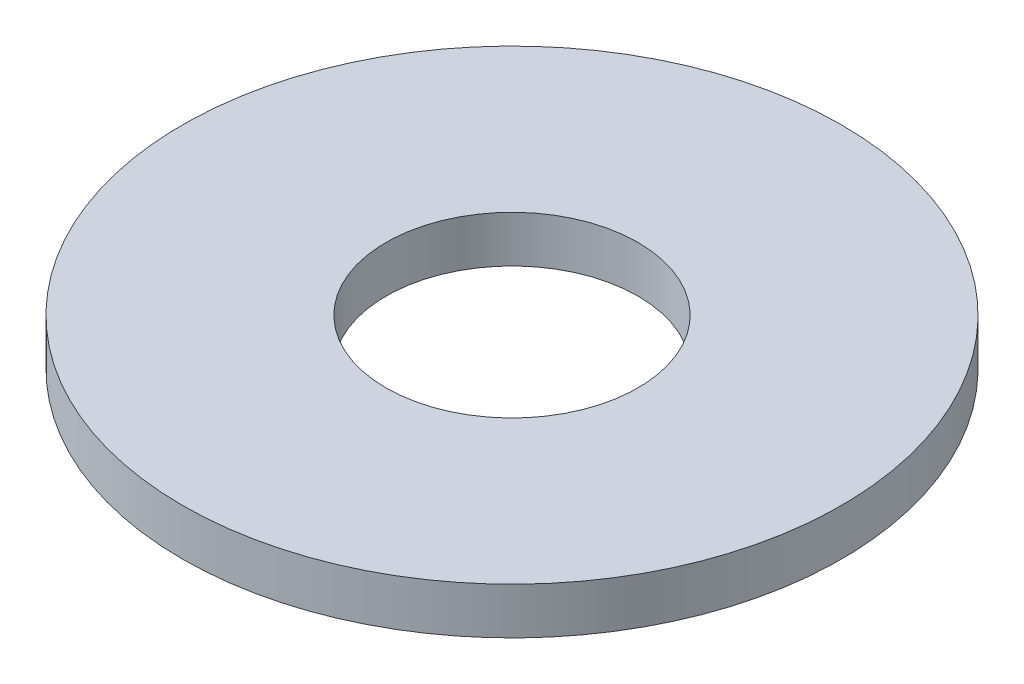
SolidWorks part; units mm, degrees
ref_plane "Front Plane" through (0, 0, 0) normal (0, 0, 1) x (1, 0, 0)
ref_plane "Top Plane" through (0, 0, 0) normal (0, 1, 0) x (1, 0, 0)
ref_plane "Right Plane" through (0, 0, 0) normal (1, 0, 0) x (0, 0, -1)
sketch "Sketch1" plane through (0, 0, 0) normal (0, 1, 0) x (1, 0, 0)
  circle A0 centre (0, 0) radius 85
  dimension "FLANGE_OD" = 170
extrude "Boss-Extrude1" add sketch "Sketch1" along normal blind 12
sketch "Sketch2" plane through (0, 0, 0) normal (0, 1, 0) x (1, 0, 0)
  circle A0 centre (0, 0) radius 32.5
  dimension "BORE_D" = 65
extrude "Cut-Extrude1" cut sketch "Sketch2" along normal through all
sketch "Sketch3" plane through (0, 12, 0) normal (0, 1, 0) x (1, 0, 0)
  circle A0 centre (0, 0) radius 22.5827 construction
  circle A1 centre (-22.5827, 0) radius 7.8536
  dimension "BOLT_D" = 15.7072
  dimension "BOLT_PCD" = 45.1655
extrude "Cut-Extrude2" cut sketch "Sketch3" against normal blind 7.9686 rebuild error yes
pattern_circular "CirPattern1" count 6 over 360 rebuild error yes
